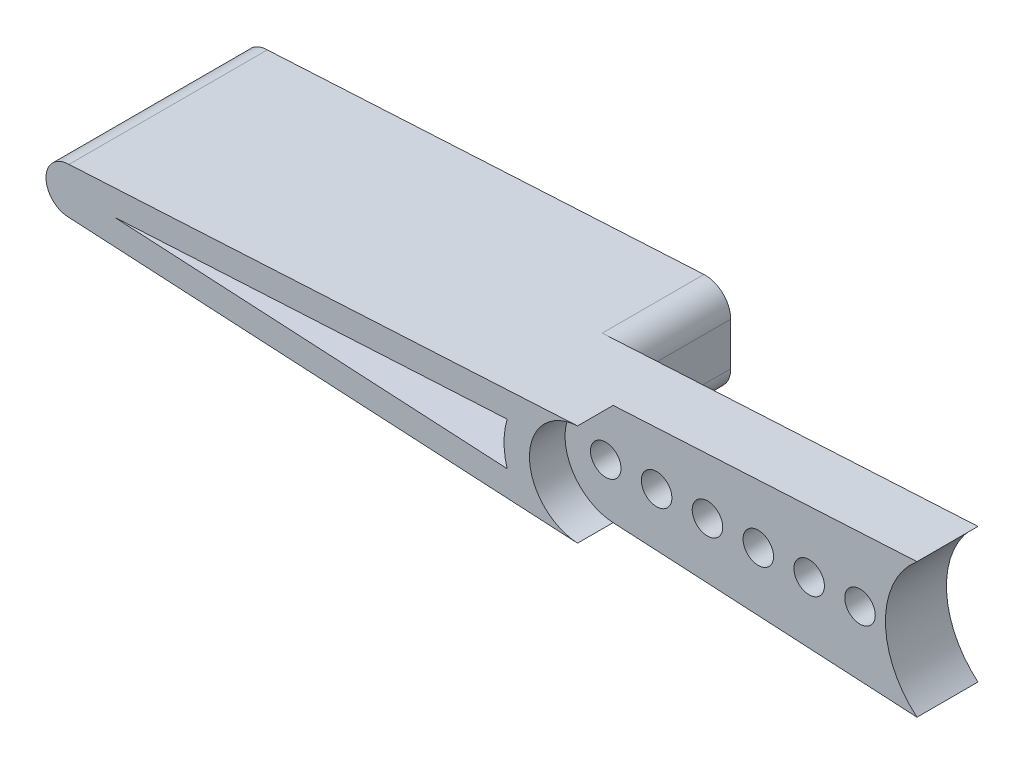
SolidWorks part; units mm, degrees
ref_plane "Front Plane" through (0, 0, 0) normal (0, 0, 1) x (1, 0, 0)
ref_plane "Top Plane" through (0, 0, 0) normal (0, 1, 0) x (1, 0, 0)
ref_plane "Right Plane" through (0, 0, 0) normal (1, 0, 0) x (0, 0, -1)
sketch "Sketch1" plane through (0, 0, 0) normal (0, 0, 1) x (1, 0, 0)
  line L2 (1.2409, 2.65) -> (-10.7091, 1.997)
  line L3 (-10.7091, -1.997) -> (1.2409, -2.65)
  line L4 (-11, 0) -> (1.358, 0) construction
  line L5 (-10.7091, 1.997) -> (-30.7114, 0.904)
  line L6 (-10.7091, -1.997) -> (-30.7114, -0.904)
  line L7 (-13.4788, 0.8442) -> (-28.9281, 0)
  line L8 (-13.4788, -0.8442) -> (-28.9281, 0)
  line L9 (-10.6546, 0.9985) -> (-28.9281, 0) construction
  line L10 (-10.6546, -0.9985) -> (-28.9281, 0) construction
  circle A2 centre (-11, 0) radius 0.6
  arc A3 (1.2409, 2.65) -> (1.2409, -2.65) centre (3.45, 0) ccw
  arc A4 (-10.7091, 1.997) -> (-10.7091, -1.997) centre (-10.6, 0) ccw
  circle A10 centre (-9, 0) radius 0.6
  circle A11 centre (-7, 0) radius 0.6
  circle A12 centre (-5, 0) radius 0.6
  circle A13 centre (-3, 0) radius 0.6
  circle A14 centre (-1, 0) radius 0.6
  arc A15 (-30.7114, 0.904) -> (-30.7114, -0.904) centre (-30.7114, 0) ccw
  arc A16 (-28.9281, 0) -> (-28.9281, 0) centre (-28.9281, 0) ccw
  arc A17 (-13.4788, 0.8442) -> (-13.4788, -0.8442) centre (-10.6, 0) ccw
  arc A18 (-10.7637, 2.9955) -> (-10.7637, -2.9955) centre (-10.6, 0) ccw construction
  point P21 (0, 0)
  point P25 (0, 0)
  dimension "D1" = 0.4
  dimension "D2" = 2
  dimension "D3" = 1.2
  dimension "D4" = 3.45
  dimension "D7" = 1.8081
  dimension "D5" = 11.95
  dimension "D6" = 3.128
  dimension "D8" = 1.997
  dimension "D9" = 5.3
  dimension "D11" = 2
  dimension "D12" = 32
  dimension "D13" = 1
  dimension "D14" = 1
  dimension "D10" = 6
extrude "Boss-Extrude1" add sketch "Sketch1" along normal blind 2.4 contours L2 A4 L3 A3 A14 A13 A12 A11 A10 A2 region at (-0.1482, 0, 0)
extrude "Boss-Extrude2" add sketch "Sketch1<4>" along normal blind 3.8 contours L5 A15 L6 A4 L7 A17 L8 region at (-12.8128, 0, 0)
sketch "Sketch1<4>" plane through (0, 0, 0) normal (0, 0, 1) x (1, 0, 0) same geometry as "Sketch1"
sketch "Sketch2" plane through (0, 0, 0) normal (0, 0, -1) x (-1, 0, 0)
  line L0 (12.4847, -0.8439) -> (12.4847, 0.8439)
  line L1 (13.4788, -0.8442) -> (28.9281, 0) construction
  line L2 (30.7114, 0.904) -> (-1.2409, 2.65)
  line L3 (-1.2409, -2.65) -> (30.7114, -0.904)
  line L4 (30.7114, 0.904) -> (13.5392, 1.8424)
  line L5 (13.5392, -1.8424) -> (30.7114, -0.904)
  line L6 (13.4788, -0.8442) -> (28.9281, 0)
  line L7 (13.4788, 0.8442) -> (28.9281, 0) construction
  line L8 (13.4788, 0.8442) -> (28.9281, 0)
  arc A0 (12.4847, 0.8439) -> (13.5392, 1.8424) centre (13.4847, 0.8439) cw
  arc A1 (12.4847, -0.8439) -> (13.5392, -1.8424) centre (13.4847, -0.8439) ccw
  arc A2 (-1.2409, -2.65) -> (-1.2409, 2.65) centre (-3.45, 0) ccw
  arc A3 (30.7114, -0.904) -> (30.7114, 0.904) centre (30.7114, 0) ccw
  arc A4 (-1.2409, -2.65) -> (-1.2409, 2.65) centre (-3.45, 0) ccw
  arc A5 (30.7114, -0.904) -> (30.7114, 0.904) centre (30.7114, 0) ccw
  arc A6 (13.4788, -0.8442) -> (13.4788, 0.8442) centre (10.6, 0) ccw construction
  arc A7 (13.4788, -0.8442) -> (13.4788, 0.8442) centre (10.6, 0) ccw
  point P10 (12.4847, 1.9)
  point P13 (12.4847, -1.9)
  line M12 (30.7114, 0.904) -> (-1.2409, 2.65)
  line M14 (-1.2409, -2.65) -> (30.7114, -0.904)
  arc M15 (30.7114, -0.904) -> (30.7114, 0.904) centre (30.7114, 0) ccw
  line M16 (13.4788, 0.8442) -> (28.9281, 0)
  line M17 (28.9281, 0) -> (13.4788, -0.8442)
  arc M18 (13.4788, -0.8442) -> (13.4788, 0.8442) centre (10.6, 0) ccw
  dimension "D3" = 1
  dimension "D2" = 3.8
  dimension "D1" = 0
extrude "Boss-Extrude3" add sketch "Sketch2" along normal blind 4 contours L0 A1 A0 M14 M15 M12 M18 M16 M17 region at (-12.6795, 0, 0)
